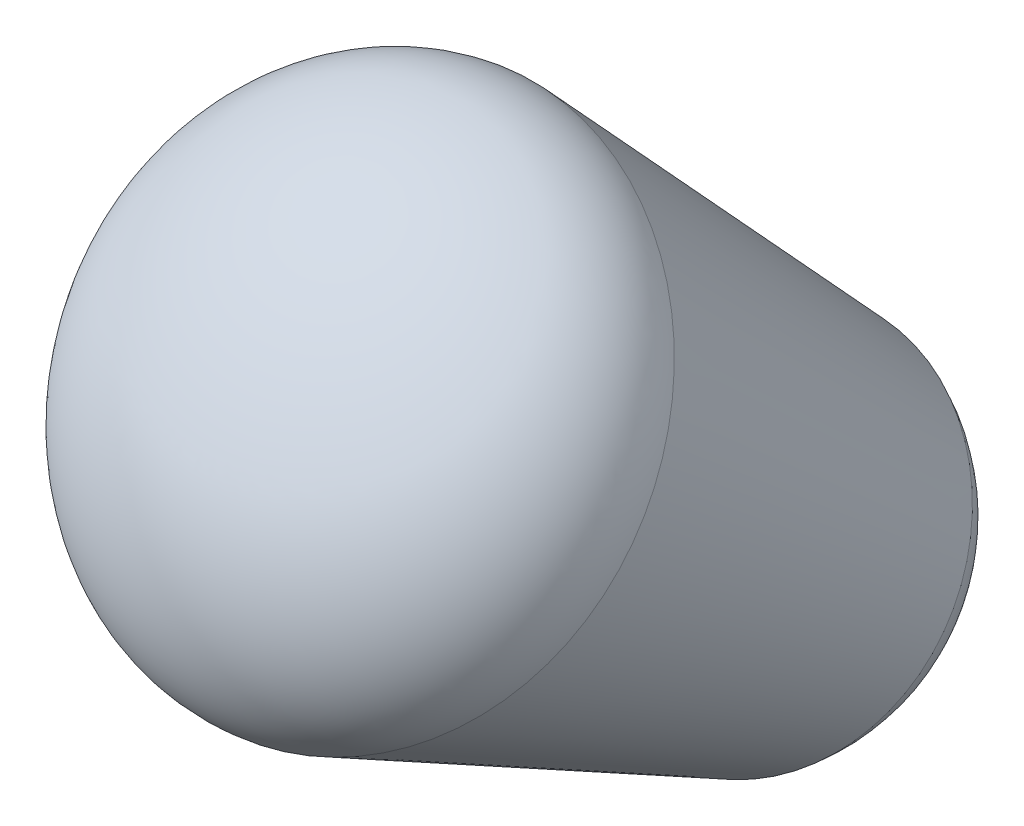
SolidWorks part; units mm, degrees
ref_plane "Front Plane" through (0, 0, 0) normal (0, 0, 1) x (1, 0, 0)
ref_plane "Top Plane" through (0, 0, 0) normal (0, 1, 0) x (1, 0, 0)
ref_plane "Right Plane" through (0, 0, 0) normal (1, 0, 0) x (0, 0, -1)
sketch "Top Contour" plane through (0, 0, 0) normal (1, 0, 0) x (0, 0, -1)
  line L0 (189.3211, -51.6959) -> (211.711, -60.626) construction
  line L1 (189.3211, -51.6959) -> (149.4591, -69.9444) construction
  line L2 (149.4591, -69.9444) -> (126.4413, -51.6959) construction
ref_plane "Plane1" through (0, -51.6959, -126.4413) normal (0, 0.6212, 0.7836) x (1, 0, 0)
sketch "Sketch1" plane through (0, -51.6959, -126.4413) normal (0, 0.6212, 0.7836) x (1, 0, 0)
  circle A0 centre (0, 0) radius 15
extrude "Boss-Extrude1" add sketch "Sketch1" against normal up to vertex (29.3739 mm away) draft 9 up to point (0, -69.9444, -149.4591)
dome "Dome1" faces to dome 1 distance 10 reverse direction no elliptical dome yes face at (0, -63.4501, -117.1226) parameters "D1"=10
dome "Dome2" faces to dome 1 distance 7 reverse direction no elliptical dome no face at (0, -78.053, -143.0306) parameters "D1"=7
ref_axis "Axis1" through (0, -51.6959, -126.4413) along (1, 0, 0)
ref_axis "Axis2" through (0, -69.9444, -149.4591) along (1, 0, 0)
